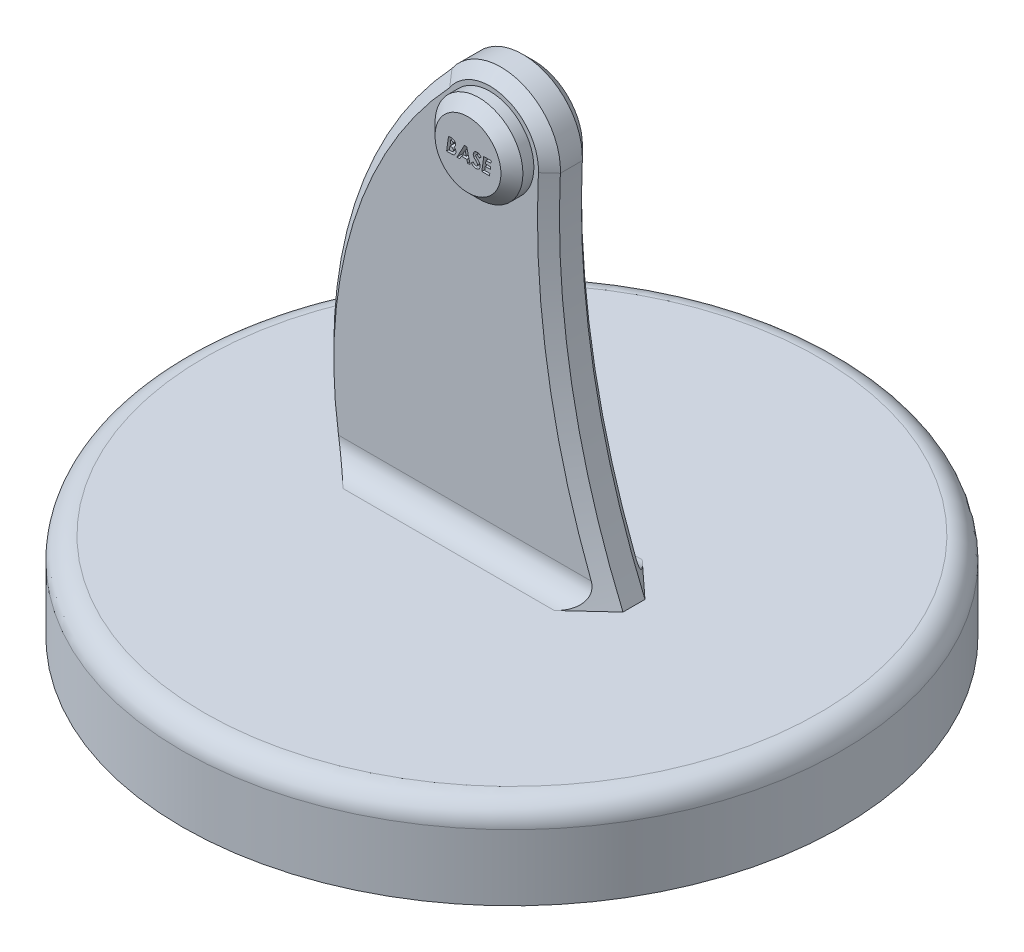
SolidWorks part; units mm, degrees
ref_plane "Front Plane" through (0, 0, 0) normal (0, 0, 1) x (1, 0, 0)
ref_plane "Top Plane" through (0, 0, 0) normal (0, 1, 0) x (1, 0, 0)
ref_plane "Right Plane" through (0, 0, 0) normal (1, 0, 0) x (0, 0, -1)
sketch "Sketch1" plane through (0, 0, 0) normal (0, 1, 0) x (1, 0, 0)
  circle A0 centre (0, 0) radius 75
  dimension "D1" = 150
extrude "Boss-Extrude1" add sketch "Sketch1" along normal blind 20
fillet "Fillet1" radius 5 1 edges at (0, 20, 75)
sketch "Sketch2" plane through (0, 0, 0) normal (0, 0, 1) x (1, 0, 0)
  line L0 (0, 0) -> (0, 100) construction
  line L1 (-75, 15) -> (75, 15) construction
  line L2 (-75, 0) -> (75, 0) construction
  line L3 (-35, 15) -> (30, 15)
  arc A0 (13.5176, 99.3495) -> (-11.1289, 107.7004) centre (0, 100) ccw
  arc A1 (-11.1289, 107.7004) -> (-35, 15) centre (61.9637, 39.4547) ccw
  arc A2 (13.5176, 99.3495) -> (30, 15) centre (193.3095, 90.6969) ccw
  dimension "D3" = 100
  dimension "D4" = 180
  dimension "D5" = 100
  dimension "D1" = 30
  dimension "D2" = 35
extrude "Boss-Extrude2" add sketch "Sketch2" along normal mid plane 10
chamfer "Chamfer1" distance 2.5 angle 45 6 edges at (-34.2062, 66.8654, -5) (16.1462, 58.8663, -5) (4.3429, 112.8174, -5) (-34.2062, 66.8654, 5) (4.3429, 112.8174, 5) (16.1462, 58.8663, 5)
fillet "Fillet2" radius 5 2 edges at (-4.2583, 20, -5) (-4.2583, 20, 5)
sketch "Sketch3" plane through (0, 0, 5) normal (0, 0, 1) x (1, 0, 0)
  circle A1 centre (0, 100) radius 10
extrude "Boss-Extrude4" add sketch "Sketch3" along normal mid plane 10
chamfer "Chamfer2" distance 2.5 angle 45 1 edges at (10, 100, 10)
sketch "Sketch4" plane through (0, 0, -5) normal (0, 0, -1) x (-1, 0, 0)
  circle A0 centre (0, 100) radius 5
  dimension "D1" = 10
extrude "Cut-Extrude1" cut sketch "Sketch4" against normal blind 10 contours A0
sketch "Sketch5" plane through (0, 0, 10) normal (0, 0, 1) x (1, 0, 0)
  text T0 "<b><i>BASE</i></b>"
  point P1 (-3.2499, 98.2239)
  point P2 (-5.7236, 98.4713)
  point P3 (-4.4867, 98.4218)
  point P4 (0, 0)
  point P5 (-5.0309, 98.2734)
extrude "Cut-Extrude2" cut sketch "Sketch5" against normal blind 2.5
